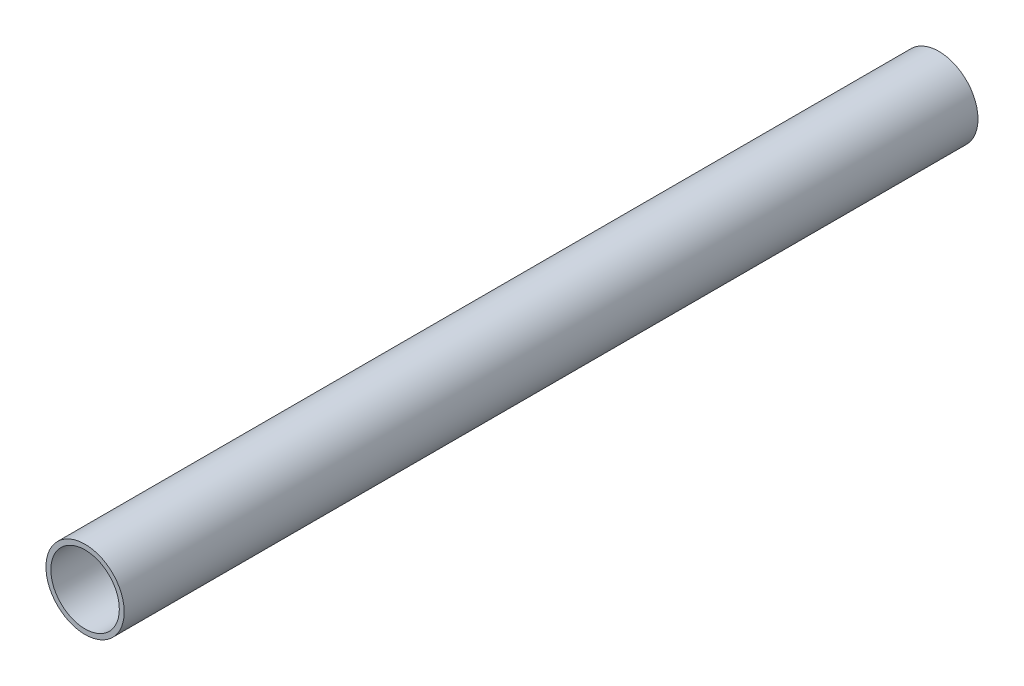
SolidWorks part; units mm, degrees
material "PC High Viscosity"
ref_plane "Front Plane" through (0, 0, 0) normal (0, 0, 1) x (1, 0, 0)
ref_plane "Top Plane" through (0, 0, 0) normal (0, 1, 0) x (1, 0, 0)
ref_plane "Right Plane" through (0, 0, 0) normal (1, 0, 0) x (0, 0, -1)
sketch "Sketch1" plane through (0, 0, 0) normal (0, 0, 1) x (1, 0, 0)
  circle A0 centre (0, 0) radius 22.225
  circle A1 centre (0, 0) radius 25.4
  dimension "D1" = 50.8
  dimension "D2" = 44.45
extrude "Boss-Extrude1" add sketch "Sketch1" along normal mid plane 554.0121
